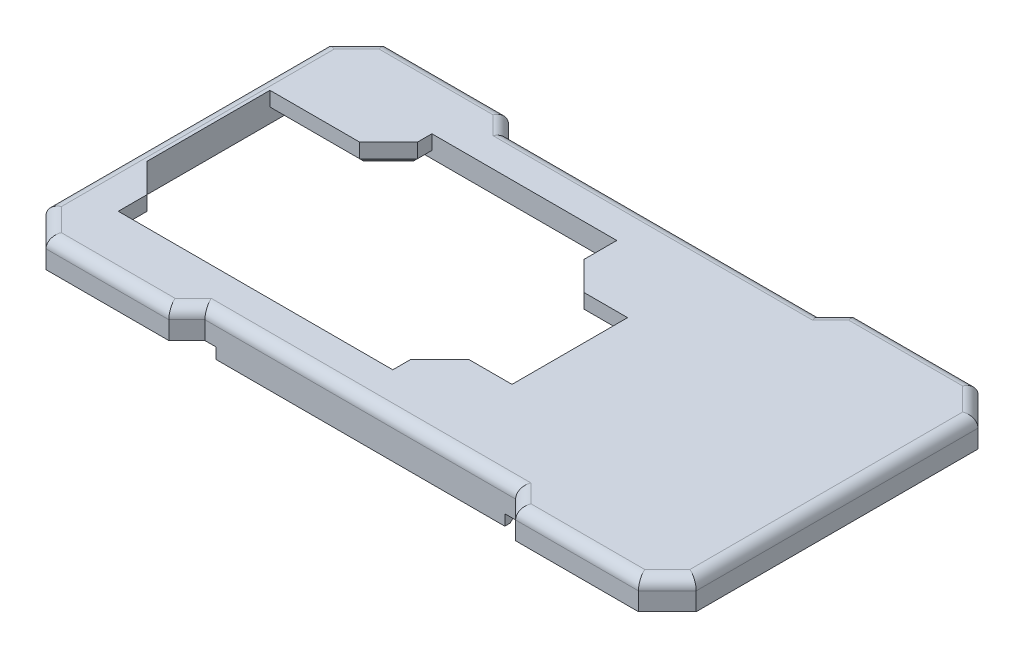
SolidWorks part; units mm, degrees
ref_plane "Front Plane" through (0, 0, 0) normal (0, 0, 1) x (1, 0, 0)
ref_plane "Top Plane" through (0, 0, 0) normal (0, 1, 0) x (1, 0, 0)
ref_plane "Right Plane" through (0, 0, 0) normal (1, 0, 0) x (0, 0, -1)
sketch "Sketch1" plane through (0, 0, 0) normal (0, 1, 0) x (1, 0, 0)
  line L1 (0, 0) -> (90, 0)
  line L2 (0, 0) -> (0, 47)
  line L3 (0, 47) -> (90, 47)
  line L4 (90, 0) -> (90, 47)
extrude "Boss-Extrude1" add sketch "Sketch1" along normal blind 4
sketch "Sketch2" plane through (0, 4, 0) normal (0, 1, 0) x (1, 0, 0)
  line L0 (0, 23.5) -> (2, 23.5) construction
  line L1 (0, 47) -> (0, 0) construction
  line L2 (2, 23.5) -> (2, 40.5)
  line L3 (2, 23.5) -> (2, 6.5)
  line L4 (2, 6.5) -> (54, 6.5)
  line L5 (2, 40.5) -> (54, 40.5)
  line L6 (54, 40.5) -> (54, 6.5)
  line L8 (0, 0) -> (90, 0) construction
  dimension "D1" = 2
  dimension "D2" = 34
  dimension "D3" = 6.5
  dimension "D4" = 52
extrude "Cut-Extrude1" cut sketch "Sketch2" along normal through all from surface starting at face at (45, 0, -23.5)
fillet "Fillet1" radius 6.4 2 edges at (2, 2, -6.5) (54, 2, -40.5)
sketch "Sketch4" plane through (0, 4, 0) normal (0, 1, 0) x (1, 0, 0)
  line L0 (0, 23.5) -> (13, 23.5) construction
  line L1 (0, 47) -> (0, 0) construction
  line L2 (13, 23.5) -> (13, 43.75) construction
  line L3 (45, 47) -> (45, 0) construction
  line L4 (90, 47) -> (0, 47) construction
  line L5 (0, 0) -> (90, 0) construction
  circle A0 centre (13, 43.75) radius 2.57
  circle A1 centre (13, 3.25) radius 2.57
  circle A2 centre (77, 3.25) radius 2.57
  circle A3 centre (77, 43.75) radius 2.57
  dimension "D1" = 13
  dimension "D2" = 20.25
extrude "Cut-Extrude3" cut sketch "Sketch4" along normal blind 3.2 from surface starting at face at (28, 0, -23.5)
sketch "Sketch5" plane through (0, 4, 0) normal (0, 1, 0) x (1, 0, 0)
  line L0 (45, 0) -> (45, 4)
  line L1 (0, 0) -> (90, 0) construction
  line L2 (45, 4) -> (65, 4)
  line L3 (65, 4) -> (65, 0)
  line L4 (65, 0) -> (45, 0)
  line L5 (45, 4) -> (25, 4)
  line L6 (25, 4) -> (25, 0)
  line L7 (25, 0) -> (45, 0)
  line L8 (0, 23.5) -> (90, 23.5) construction
  line L9 (0, 47) -> (0, 0) construction
  line L10 (90, 0) -> (90, 47) construction
  line L11 (25, 47) -> (45, 47)
  line L12 (25, 43) -> (25, 47)
  line L13 (45, 43) -> (25, 43)
  line L14 (65, 47) -> (45, 47)
  line L15 (65, 43) -> (65, 47)
  line L16 (45, 43) -> (65, 43)
  line L17 (45, 47) -> (45, 43)
  line M15 (0, 0) -> (90, 0)
  line M19 (90, 47) -> (0, 47)
  dimension "D1" = 4
  dimension "D2" = 20
  dimension "D3" = 20
extrude "Cut-Extrude4" cut sketch "Sketch5" against normal blind 21.1 contours L5 L6 L0 M15 | L3 L2 L0 M15 | L17 L12 L13 M19 | L17 L16 L15 M19 region at (35, 4, -2) region at (55, 4, -2) region at (35, 4, -45) region at (55, 4, -45)
chamfer "Chamfer1" distance 4 angle 45 8 edges at (90, 2, 0) (90, 2, -47) (0, 2, -47) (0, 2, 0) (25, 2, -47) (65, 2, -47) (65, 2, 0) (25, 2, 0)
sketch "Sketch6" plane through (0, 4, 0) normal (0, 1, 0) x (1, 0, 0)
  line L0 (54, 6.5) -> (54, 14.5)
  line L1 (54, 34.1) -> (54, 6.5) construction
  line L2 (54, 14.5) -> (44, 14.5)
  line L3 (44, 14.5) -> (44, 8)
  line L4 (54, 6.5) -> (8.4, 6.5) construction
  line L5 (42, 6.5) -> (54, 6.5)
  line L6 (44, 8) -> (6, 8)
  line L7 (6, 8) -> (6, 16)
  line L8 (6, 16) -> (2, 16)
  line L9 (2, 12.9) -> (2, 40.5) construction
  line L10 (2, 16) -> (2, 6.5)
  line L11 (2, 6.5) -> (42, 6.5)
  line L12 (47.6, 40.5) -> (54, 40.5)
  line L13 (54, 40.5) -> (54, 30.5)
  line L14 (54, 30.5) -> (44, 30.5)
  line L15 (44, 30.5) -> (44, 39)
  line L17 (2, 40.5) -> (2, 33)
  line L18 (2, 33) -> (18.4128, 33)
  line L19 (44, 39) -> (18.4128, 39)
  line L20 (18.4128, 39) -> (18.4128, 33)
  line L21 (2, 40.5) -> (47.6, 40.5)
  dimension "D1" = 8
  dimension "D2" = 10
  dimension "D3" = 6.5
  dimension "D4" = 10
  dimension "D5" = 4
  dimension "D6" = 9.5
  dimension "D7" = 7.5
extrude "Boss-Extrude2" add sketch "Sketch6" against normal blind 3
chamfer "Chamfer2" distance 4 angle 45 3 edges at (18.4128, 2.5, -33) (44, 2.5, -14.5) (44, 2.5, -30.5)
chamfer "Chamfer3" distance 4 angle 45 1 edges at (6, 2.5, -16)
sketch "Sketch7" plane through (0, 0, 0) normal (0, -1, 0) x (1, 0, 0)
  line L0 (65, -22.5) -> (56, -22.5)
  line L3 (56, -40.5) -> (74, -40.5)
  line L4 (74, -40.5) -> (74, -22.5)
  line L5 (56, -6.5) -> (74, -6.5)
  line L6 (57.5, -6.5) -> (72.5, -6.5) construction
  line L7 (56, -40.5) -> (56, -22.5)
  line L8 (57.5, -22.5) -> (72.5, -22.5) construction
  line L9 (65, -22.5) -> (74, -22.5)
  line L10 (65, -21.5) -> (74, -21.5)
  line L11 (72.5, -21.5) -> (57.5, -21.5) construction
  line L12 (65, -21.5) -> (56, -21.5)
  line L16 (88, -40.5) -> (88, -6.5)
  line L17 (88, -6.5) -> (76, -6.5)
  line L18 (76, -6.5) -> (76, -40.5)
  line L19 (88, -40.5) -> (76, -40.5)
  line L20 (74, -21.5) -> (74, -6.5)
  line L21 (56, -21.5) -> (56, -6.5)
  point P9 (65, -6.5)
extrude "Cut-Extrude5" cut sketch "Sketch7" against normal blind 2.5
fillet "Fillet2" radius 1.5 12 edges at (56, 1.25, -40.5) (74, 1.25, -22.5) (74, 1.25, -21.5) (74, 1.25, -40.5) (76, 1.25, -40.5) (88, 1.25, -40.5) (74, 1.25, -6.5) (76, 1.25, -6.5) (88, 1.25, -6.5) (56, 1.25, -6.5) (56, 1.25, -22.5) (56, 1.25, -21.5)
chamfer "Chamfer4" distance 1 angle 45 11 edges at (51, 1, -14.5) (46, 1, -12.5) (44, 1, -9.25) (6, 1, -10) (4, 1, -14) (8.2064, 1, -33) (16.4128, 1, -35) (18.4128, 1, -38) (44, 1, -36.75) (51, 1, -30.5) (46, 1, -32.5)
sketch "Sketch8" plane through (0, 4, 0) normal (0, 1, 0) x (1, 0, 0)
  line L0 (45, 4) -> (45, 2.5)
  line L1 (65, 4) -> (25, 4) construction
  line L2 (45, 2.5) -> (66.5, 2.5)
  line L3 (65, 4) -> (69, 0) construction
  line L4 (66.5, 2.5) -> (65, 4)
  line L5 (65, 4) -> (25, 4)
  line L6 (25, 4) -> (23.5, 2.5)
  line L7 (21, 0) -> (25, 4) construction
  line L8 (23.5, 2.5) -> (45, 2.5)
  line L9 (90, 23.5) -> (74.5605, 23.5) construction
  line L11 (23.5, 44.5) -> (45, 44.5)
  line L12 (25, 43) -> (23.5, 44.5)
  line L13 (65, 43) -> (25, 43)
  line L14 (66.5, 44.5) -> (65, 43)
  line L15 (45, 44.5) -> (66.5, 44.5)
  line L16 (45, 43) -> (45, 44.5)
  line M22 (65, 43) -> (25, 43)
  line M23 (25, 43) -> (21, 47)
  line M29 (21, 0) -> (25, 4)
  line M30 (25, 4) -> (65, 4)
  line M31 (65, 4) -> (69, 0)
  line M37 (69, 47) -> (65, 43)
extrude "Boss-Extrude3" add sketch "Sketch8" against normal blind 5.5 contours L0 L2 M31 M30 | L8 L0 M29 M30 | L16 L15 M22 M37 | L13 L16 L11 M23 region at (55.3795, 4, -3.241) region at (34.6205, 4, -3.241) region at (34.6205, 4, -43.759) region at (55.3795, 4, -43.759)
sketch "Sketch10" plane through (0, -1.5, 0) normal (0, -1, 0) x (-1, 0, 0)
  line L0 (-25, 4) -> (-25, 2.5)
  line L1 (-23.5, 2.5) -> (-66.5, 2.5) construction
  line L2 (-25, 2.5) -> (-23.5, 2.5)
  line L3 (-23.5, 2.5) -> (-25, 4)
  line L4 (-65, 4) -> (-65, 2.5)
  line L5 (-65, 2.5) -> (-66.5, 2.5)
  line L6 (-66.5, 2.5) -> (-65, 4)
  line L7 (-65, 43) -> (-65, 44.5)
  line L8 (-23.5, 44.5) -> (-66.5, 44.5) construction
  line L9 (-65, 44.5) -> (-66.5, 44.5)
  line L10 (-66.5, 44.5) -> (-65, 43)
  line L11 (-25, 43) -> (-25, 44.5)
  line L12 (-25, 44.5) -> (-23.5, 44.5)
  line L13 (-23.5, 44.5) -> (-25, 43)
extrude "Cut-Extrude6" cut sketch "Sketch10" against normal up to surface (1.5 mm away) up to face at (82, 0, -23.5)
fillet "Fillet3" radius 1.5 16 edges at (77.5, 4, 0) (88, 4, -2) (67.75, 4, -1.25) (67.75, 4, -45.75) (77.5, 4, -47) (88, 4, -45) (90, 4, -23.5) (22.25, 4, -45.75) (45, 4, -44.5) (2, 4, -45) (12.5, 4, -47) (0, 4, -23.5) (2, 4, -2) (12.5, 4, 0) (22.25, 4, -1.25) (45, 4, -2.5)
sketch "Sketch11" plane through (0, 0, 0) normal (0, -1, 0) x (1, 0, 0)
  line L0 (0, -23.5) -> (0, -16.5)
  line L1 (0, -43) -> (0, -4) construction
  line L2 (0, -16.5) -> (1.25, -16.5)
  line L3 (0, -23.5) -> (0, -30.5)
  line L4 (0, -30.5) -> (1.25, -30.5)
  line L5 (1.25, -30.5) -> (1.25, -16.5)
extrude "Boss-Extrude4" add sketch "Sketch11" along normal up to surface (1.5 mm away) up to face at (45, -1.5, -43.75)
chamfer "Chamfer6" distance 0.75 angle 45 3 edges at (45, -1.5, -43) (45, -1.5, -4) (1.25, -1.5, -23.5)
